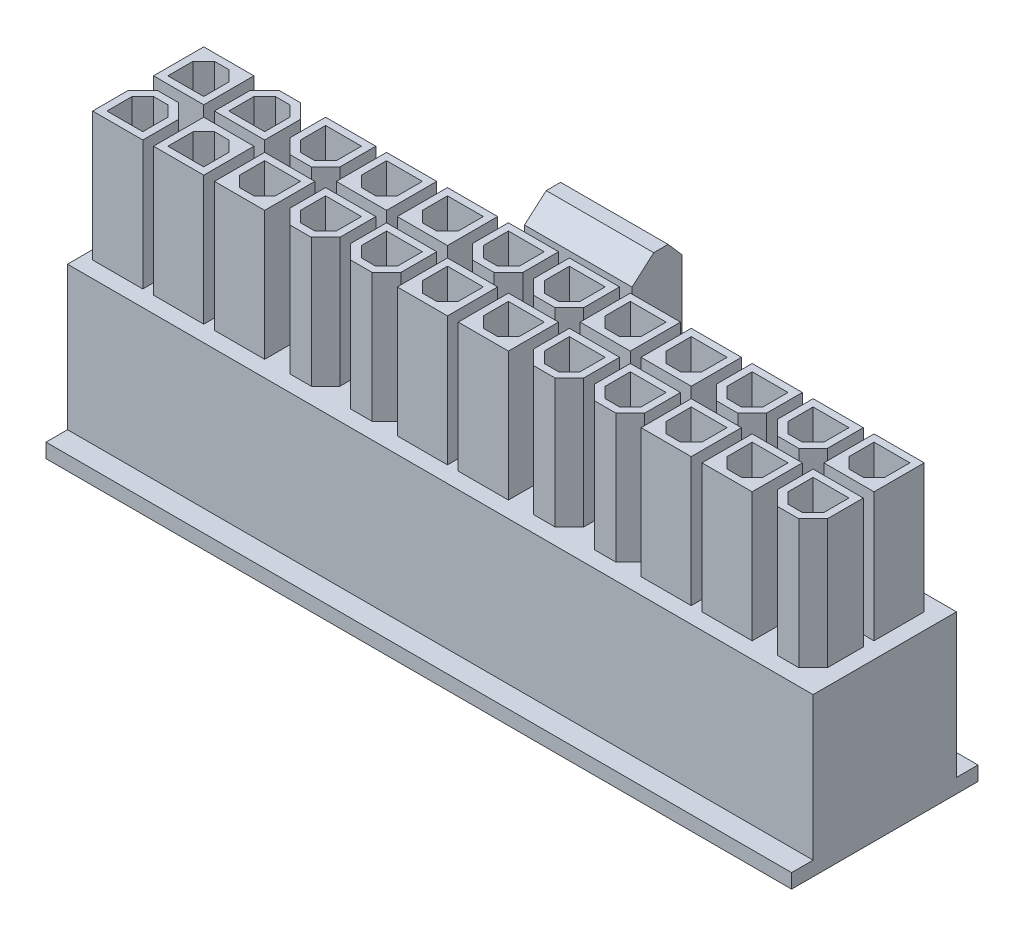
SolidWorks part; units mm, degrees
ref_plane "Ebene vorne" through (0, 0, 0) normal (0, 0, 1) x (1, 0, 0)
ref_plane "Ebene oben" through (0, 0, 0) normal (0, 1, 0) x (1, 0, 0)
ref_plane "Ebene rechts" through (0, 0, 0) normal (1, 0, 0) x (0, 0, -1)
sketch "Skizze1" plane through (0, 0, 0) normal (1, 0, 0) x (0, 0, -1)
  line L1 (5, 0) -> (-5, 0)
  line L2 (5, 0) -> (5, 11)
  line L3 (5, 11) -> (-5, 11)
  line L4 (-5, 0) -> (-5, 11)
  point P4 (0, 0)
  dimension "D1" = 10
  dimension "D2" = 11
extrude "Aufsatz-Linear austragen1" add sketch "Skizze1" along normal mid plane 52
sketch "Skizze2" plane through (0, 0, 0) normal (1, 0, 0) x (0, 0, -1)
  line L0 (0, 0) -> (0, 11) construction
  line L1 (-5, 0) -> (-6.5, 0)
  line L2 (-5, 0) -> (-5, 1)
  line L3 (-5, 1) -> (-6.5, 1)
  line L4 (-6.5, 0) -> (-6.5, 1)
  line L5 (5, 11) -> (-5, 11) construction
  line L6 (6.5, 0) -> (6.5, 1)
  line L7 (5, 1) -> (6.5, 1)
  line L8 (5, 0) -> (5, 1)
  line L9 (5, 0) -> (6.5, 0)
  dimension "D1" = 1.5
  dimension "D2" = 1
extrude "Aufsatz-Linear austragen2" add sketch "Skizze2" along normal mid plane 52
sketch "Skizze3" plane through (0, 0, 0) normal (1, 0, 0) x (0, 0, -1)
  line L0 (5, 11) -> (5.5717, 11)
  line L1 (7.5, 8.198) -> (7.5, 5.198)
  line L2 (7.5, 5.198) -> (8.5, 4)
  line L3 (8.5, 4) -> (8.5, 2)
  line L4 (8.5, 2) -> (6.5, 2)
  line L5 (6.5, 2) -> (6.5, 8)
  line L6 (6.5, 8) -> (5, 8)
  line L7 (5, 1) -> (5, 11) construction
  line L8 (5, 11) -> (5, 8)
  line L9 (-6.5, 0) -> (6.5, 0) construction
  arc A0 (5.5717, 11) -> (6.5359, 9.599) centre (7.0717, 11) ccw
  arc A1 (6.5359, 9.599) -> (7.5, 8.198) centre (6, 8.198) cw
  dimension "D5" = 1.5
  dimension "D1" = 2
  dimension "D2" = 1
  dimension "D3" = 2
  dimension "D4" = 2
  dimension "D6" = 3
  dimension "D7" = 1.5
  dimension "D8" = 3
extrude "Aufsatz-Linear austragen3" add sketch "Skizze3" along normal mid plane 10
sketch "Skizze4" plane through (0, 0, 0) normal (0, -1, 0) x (1, 0, 0)
  line L0 (26, -5) -> (-26, -5) construction
  line L1 (-3.5, -5) -> (3.5, -5)
  line L2 (-3.5, -5) -> (-3.5, -6.5)
  line L3 (-3.5, -6.5) -> (3.5, -6.5)
  line L4 (3.5, -5) -> (3.5, -6.5)
  line L5 (26, -6.5) -> (-26, -6.5) construction
  line L6 (0, -5) -> (0, 0) construction
  line L7 (-5, -6.5) -> (-5, -8.5) construction
  dimension "D1" = 1.5
extrude "Schnitt-Linear austragen1" cut sketch "Skizze4" against normal through all
sketch "Skizze5" plane through (0, 0, 0) normal (1, 0, 0) x (0, 0, -1)
  line L0 (8.1235, 4.451) -> (8.1235, 19.8707)
  line L1 (8.5, 4) -> (7.5, 5.198) construction
  line L2 (8.1235, 19.8707) -> (7.1363, 21)
  line L3 (7.1363, 21) -> (6.1363, 21)
  line L4 (6.1363, 21) -> (4.6235, 19.6776)
  line L5 (4.6235, 19.6776) -> (4.6235, 17.6776)
  line L6 (4.6235, 17.6776) -> (6.1235, 17.6776)
  line L7 (6.1235, 17.6776) -> (6.5, 8)
  line L8 (6.5, 8) -> (6.5, 2)
  line L9 (6.5, 2) -> (8.1235, 4.451)
  line L10 (5, 11) -> (-5, 11) construction
  dimension "D1" = 3.5
  dimension "D2" = 1.5
  dimension "D3" = 1
  dimension "D4" = 10
  dimension "D5" = 2
  dimension "D6" = 2.0093
  dimension "D7" = 1.5
extrude "Aufsatz-Linear austragen4" add sketch "Skizze5" along normal mid plane 7.5
sketch "Skizze6" plane through (0, 0, 0) normal (0, -1, 0) x (1, 0, 0)
  line L0 (-26, 6.5) -> (-26, -6.5) construction
  line L1 (-25.5, -4) -> (-21.75, -4)
  line L2 (-25.5, -4) -> (-25.5, -0.25)
  line L3 (-25.5, -0.25) -> (-21.75, -0.25)
  line L4 (-21.75, -4) -> (-21.75, -0.25)
  line L5 (-3.5, -5) -> (-26, -5) construction
  dimension "D1" = 0.5
  dimension "D2" = 1
  dimension "D3" = 3.75
extrude "Schnitt-Linear austragen2" cut sketch "Skizze6" against normal blind 10
pattern_linear "Lineares Muster1" count 12 spacing 4.25 along (1, 0, 0) count 2 spacing 4.25 along (0, 0, 1) of "Schnitt-Linear austragen2"
sketch "Skizze7" plane through (0, 11, 0) normal (0, 1, 0) x (1, 0, 0)
  line L0 (21.25, 4) -> (25, 4) construction
  line L1 (21.375, 3.875) -> (24.875, 3.875)
  line L2 (21.375, 3.875) -> (21.375, 0.375)
  line L3 (21.375, 0.375) -> (24.875, 0.375)
  line L4 (24.875, 3.875) -> (24.875, 0.375)
  line L6 (23.125, 0.25) -> (23.125, 4) construction
  line L7 (25, 0.25) -> (21.25, 0.25) construction
  line L8 (21.25, 2.125) -> (25, 2.125) construction
  line L9 (21.25, 0.25) -> (21.25, 4) construction
  line L10 (25, 4) -> (25, 0.25) construction
  point P7 (21.375, 2.125)
  point P8 (23.125, 3.875)
  dimension "D1" = 3.5
extrude "Aufsatz-Linear austragen5" add sketch "Skizze7" along normal blind 9
pattern_linear "Lineares Muster2" count 12 spacing 4.25 along (-1, 0, 0) count 2 spacing 4.25 along (0, 0, 1) skipping (0, 1), (1, 0), (2, 0), (3, 1), (4, 1), (5, 0), (6, 0), (7, 1), (8, 1), (9, 0), (10, 0), (11, 1) of "Aufsatz-Linear austragen5"
sketch "Skizze9" plane through (0, 11, 0) normal (0, 1, 0) x (1, 0, 0)
  line L0 (21.25, -2.125) -> (25, -2.125) construction
  line L1 (21.25, -4) -> (21.25, -0.25) construction
  line L2 (25, -0.25) -> (25, -4) construction
  line L3 (23.125, -0.25) -> (23.125, -4) construction
  line L4 (21.25, -0.25) -> (25, -0.25) construction
  line L5 (25, -4) -> (21.25, -4) construction
  line L6 (24.875, -2.875) -> (23.875, -3.875)
  line L7 (21.375, -0.375) -> (24.875, -0.375)
  line L8 (21.375, -0.375) -> (21.375, -2.875)
  line L9 (22.375, -3.875) -> (23.875, -3.875)
  line L10 (24.875, -0.375) -> (24.875, -2.875)
  line L11 (21.375, -0.375) -> (24.875, -3.875) construction
  line L12 (21.375, -3.875) -> (24.875, -0.375) construction
  line L13 (21.375, -2.875) -> (22.375, -3.875)
  point P12 (23.125, -2.125)
  dimension "D1" = 3.5
  dimension "D2" = 3.5
extrude "Aufsatz-Linear austragen6" add sketch "Skizze9" along normal up to surface (9 mm away) up to face at (23.125, 20, -2.125)
pattern_linear "Lineares Muster3" count 12 spacing 4.25 along (-1, 0, 0) count 2 spacing 4.25 along (0, 0, -1) skipping (0, 1), (1, 0), (2, 0), (3, 1), (4, 1), (5, 0), (6, 0), (7, 1), (8, 1), (9, 0), (10, 0), (10, 1), (11, 0), (11, 1) of "Aufsatz-Linear austragen6"
sketch "Skizze10" plane through (0, 11, 0) normal (0, 1, 0) x (1, 0, 0)
  line L0 (-19.375, 4) -> (-19.375, 0.25) construction
  line L1 (-21.25, 4) -> (-17.5, 4) construction
  line L2 (-17.5, 0.25) -> (-21.25, 0.25) construction
  line L3 (-21.25, 2.125) -> (-17.5, 2.125) construction
  line L4 (-21.25, 0.25) -> (-21.25, 4) construction
  line L5 (-17.5, 4) -> (-17.5, 0.25) construction
  line L6 (-18.625, 3.875) -> (-17.625, 2.875)
  line L7 (-20.125, 3.875) -> (-18.625, 3.875)
  line L8 (-21.125, 2.875) -> (-21.125, 0.375)
  line L9 (-21.125, 0.375) -> (-17.625, 0.375)
  line L10 (-17.625, 2.875) -> (-17.625, 0.375)
  line L11 (-21.125, 3.875) -> (-17.625, 0.375) construction
  line L12 (-21.125, 0.375) -> (-17.625, 3.875) construction
  line L13 (-21.125, 2.875) -> (-20.125, 3.875)
  point P12 (-19.375, 2.125)
  dimension "D1" = 3.5
  dimension "D2" = 3.5
extrude "Aufsatz-Linear austragen7" add sketch "Skizze10" along normal up to surface (9 mm away) up to face at (23.125, 20, -2.125)
pattern_linear "Lineares Muster4" count 2 spacing 4.25 along (-1, 0, 0) count 2 spacing 4.25 along (0, 0, 1) skipping (0, 1), (1, 0) of "Aufsatz-Linear austragen7"
sketch "Skizze11" plane through (0, 20, 0) normal (0, 1, 0) x (1, 0, 0)
  line L0 (21.25, -2.125) -> (25, -2.125) construction
  line L1 (21.25, -4) -> (21.25, -0.25) construction
  line L2 (25, -0.25) -> (25, -4) construction
  line L3 (23.125, -0.25) -> (23.125, -4) construction
  line L4 (21.25, -0.25) -> (25, -0.25) construction
  line L5 (25, -4) -> (21.25, -4) construction
  line L6 (23.625, -3.375) -> (24.375, -2.625)
  line L7 (22.625, -3.375) -> (23.625, -3.375)
  line L8 (21.875, -2.625) -> (21.875, -0.875)
  line L9 (21.875, -0.875) -> (24.375, -0.875)
  line L10 (24.375, -2.625) -> (24.375, -0.875)
  line L11 (21.875, -3.375) -> (24.375, -0.875) construction
  line L12 (21.875, -0.875) -> (24.375, -3.375) construction
  line L13 (21.875, -2.625) -> (22.625, -3.375)
  point P12 (23.125, -2.125)
  dimension "D1" = 2.5
  dimension "D2" = 2.5
extrude "Schnitt-Linear austragen3" cut sketch "Skizze11" against normal through all
pattern_linear "Lineares Muster5" count 10 spacing 4.25 along (-1, 0, 0) count 2 spacing 4.25 along (0, 0, -1) of "Schnitt-Linear austragen3"
sketch "Skizze12" plane through (0, 20, 0) normal (0, 1, 0) x (1, 0, 0)
  line L0 (-21.25, 2.125) -> (-17.5, 2.125) construction
  line L1 (-21.25, 0.25) -> (-21.25, 4) construction
  line L2 (-17.5, 4) -> (-17.5, 0.25) construction
  line L3 (-19.375, 4) -> (-19.375, 0.25) construction
  line L4 (-21.25, 4) -> (-17.5, 4) construction
  line L5 (-17.5, 0.25) -> (-21.25, 0.25) construction
  line L6 (-20.625, 2.625) -> (-19.875, 3.375)
  line L7 (-19.875, 3.375) -> (-18.875, 3.375)
  line L8 (-20.625, 2.625) -> (-20.625, 0.875)
  line L9 (-20.625, 0.875) -> (-18.125, 0.875)
  line L10 (-18.125, 2.625) -> (-18.125, 0.875)
  line L11 (-20.625, 3.375) -> (-18.125, 0.875) construction
  line L12 (-20.625, 0.875) -> (-18.125, 3.375) construction
  line L13 (-18.875, 3.375) -> (-18.125, 2.625)
  point P12 (-19.375, 2.125)
  dimension "D1" = 2.5
  dimension "D2" = 2.5
extrude "Schnitt-Linear austragen4" cut sketch "Skizze12" against normal through all
pattern_linear "Lineares Muster6" count 2 spacing 4.25 along (-1, 0, 0) count 2 spacing 4.25 along (0, 0, 1) of "Schnitt-Linear austragen4"
